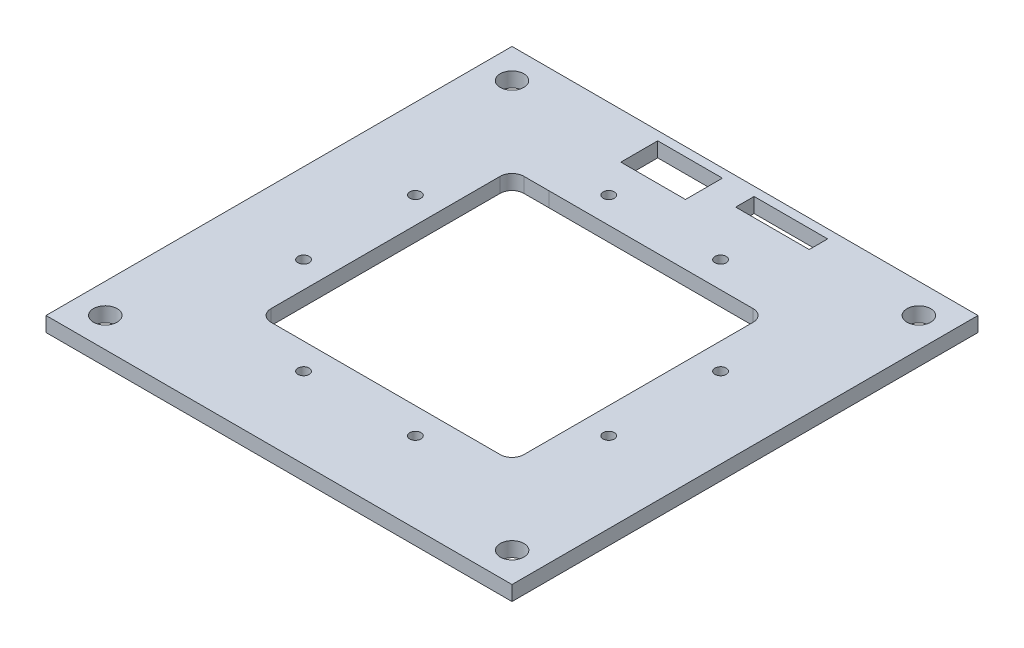
SolidWorks part; units mm, degrees
ref_plane "Front Plane" through (0, 0, 0) normal (0, 0, 1) x (1, 0, 0)
ref_plane "Top Plane" through (0, 0, 0) normal (0, 1, 0) x (1, 0, 0)
ref_plane "Right Plane" through (0, 0, 0) normal (1, 0, 0) x (0, 0, -1)
sketch "Sketch1" plane through (0, 0, 0) normal (0, 1, 0) x (1, 0, 0)
  line L0 (-100.0125, 99.9889) -> (-87.3125, 99.9889) construction
  line L1 (-100.0125, -100.0361) -> (100.0125, -100.0361)
  line L2 (-100.0125, -100.0361) -> (-100.0125, 99.9889)
  line L3 (-100.0125, 99.9889) -> (100.0125, 99.9889)
  line L4 (100.0125, -100.0361) -> (100.0125, 99.9889)
  line L5 (-100.0125, -100.0361) -> (100.0125, 99.9889) construction
  line L6 (-100.0125, 99.9889) -> (100.0125, -100.0361) construction
  line L7 (-74.6125, -74.6125) -> (74.6125, -74.6125) construction
  line L8 (-74.6125, -74.6125) -> (-74.6125, 74.6125) construction
  line L9 (-74.6125, 74.6125) -> (74.6125, 74.6125) construction
  line L10 (74.6125, -74.6125) -> (74.6125, 74.6125) construction
  line L11 (-74.6125, -74.6125) -> (74.6125, 74.6125) construction
  line L12 (-74.6125, 74.6125) -> (74.6125, -74.6125) construction
  line L13 (-87.3125, 99.9889) -> (-87.3125, -100.0361) construction
  line L14 (0, -55) -> (0, 55) construction
  line L15 (-55, 0) -> (55, 0) construction
  line L16 (-100.0125, 96.1789) -> (100.0125, 96.1789) construction
  line L18 (-33.6459, 96.1789) -> (-5.887, 96.1789)
  line L19 (-33.6459, 96.1789) -> (-33.6459, 80.3284)
  line L20 (-33.6459, 80.3284) -> (-5.887, 80.3284)
  line L21 (-5.887, 96.1789) -> (-5.887, 80.3284)
  line L22 (7.7239, 96.1789) -> (39.2871, 96.1789)
  line L23 (7.7239, 96.1789) -> (7.7239, 88.2654)
  line L24 (7.7239, 88.2654) -> (39.2871, 88.2654)
  line L25 (39.2871, 96.1789) -> (39.2871, 88.2654)
  line L33 (54.27, -38.5) -> (54.27, 38.5)
  line L47 (54.27, -38.5) -> (54.27, -42.77)
  line L54 (42.77, -54.27) -> (38.5, -54.27)
  line L56 (38.5, -54.27) -> (-38.5, -54.27)
  line L57 (-42.77, -54.27) -> (-38.5, -54.27)
  line L64 (38.5, 54.27) -> (54.2936, 54.27)
  line L67 (-54.27, -38.5) -> (-54.27, 38.5)
  line L69 (54.2936, 54.27) -> (54.27, 38.5)
  line L70 (49, -49) -> (-49, 49) construction
  line L71 (49, 49) -> (-49, -49) construction
  line L72 (42.77, -54.27) -> (54.2464, -54.27)
  line L73 (54.2464, -54.27) -> (54.27, -42.77)
  line L74 (-54.27, 38.5) -> (-54.27, 54.2464)
  line L75 (-54.27, 54.2464) -> (-38.5, 54.27)
  line L76 (0, 53) -> (0, -53) construction
  line L78 (-54.27, -38.5) -> (-54.27, -54.2936)
  line L83 (-54.27, -54.2936) -> (-42.77, -54.27)
  line L86 (-38.5, 54.27) -> (38.5, 54.27)
  circle A0 centre (-87.3125, 87.2889) radius 5.08
  circle A1 centre (87.3125, 87.2889) radius 5.08
  circle A2 centre (-87.3125, -87.2889) radius 5.08
  circle A3 centre (87.3125, -87.2889) radius 5.08
  point P6 (0, 54.27)
  point P11 (-87.3125, 87.2889)
  point P37 (0, 0)
  point P43 (0, 0)
  point P44 (0, 0)
  point P45 (0, 0)
  point P49 (0, 0)
  point P60 (0, -54.27)
  dimension "D5" = 10.16
  dimension "D7" = 85.54
  dimension "D1" = 200.025
  dimension "D2" = 200.025
  dimension "D3" = 149.225
  dimension "D4" = 12.7
  dimension "D6" = 3.81
extrude "Boss-Extrude1" add sketch "Sketch1" along normal blind 6.35
fillet "Fillet1" radius 5.08 4 edges at (54.2464, 3.175, 54.27) (-54.27, 3.175, 54.2936) (54.2936, 3.175, -54.27) (-54.27, 3.175, -54.2464)
sketch "Sketch3" plane through (0, 0, 0) normal (0, -1, 0) x (1, 0, 0)
  circle A0 centre (-24, 65.5) radius 2.4 construction
  circle A1 centre (24, 65.5) radius 2.4 construction
  circle A2 centre (-24, 65.5) radius 2.4
  circle A3 centre (24, 65.5) radius 2.4
  circle A4 centre (65.5, -24) radius 2.4
  circle A5 centre (65.5, 24) radius 2.4
  circle A6 centre (-24, -65.5) radius 2.4
  circle A7 centre (24, -65.5) radius 2.4
  circle A8 centre (-65.5, 24) radius 2.4
  circle A9 centre (-65.5, -24) radius 2.4
  dimension "D1" = 4
extrude "Cut-Extrude1" cut sketch "Sketch3" against normal through all
